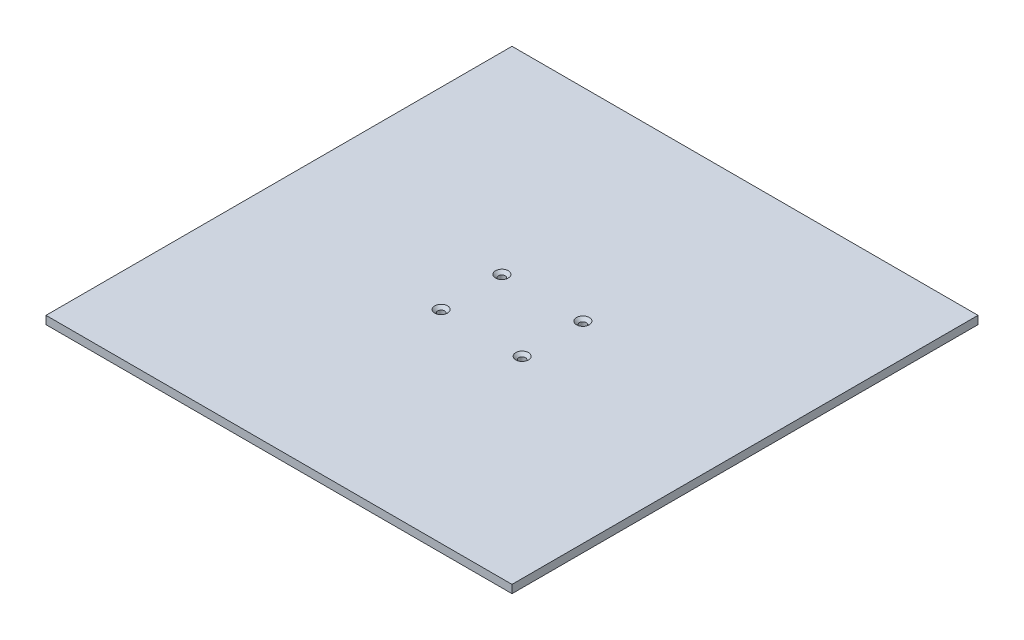
SolidWorks part; units mm, degrees
ref_plane "Front Plane" through (0, 0, 0) normal (0, 0, 1) x (1, 0, 0)
ref_plane "Top Plane" through (0, 0, 0) normal (0, 1, 0) x (1, 0, 0)
ref_plane "Right Plane" through (0, 0, 0) normal (1, 0, 0) x (0, 0, -1)
sketch "Sketch1" plane through (0, 0, 0) normal (0, 1, 0) x (1, 0, 0)
  line L1 (-115, -115) -> (115, -115)
  line L2 (-115, -115) -> (-115, 115)
  line L3 (-115, 115) -> (115, 115)
  line L4 (115, -115) -> (115, 115)
  line L5 (-115, -115) -> (115, 115) construction
  line L6 (-115, 115) -> (115, -115) construction
  point P0 (0, 0)
  dimension "D1" = 230
extrude "Boss-Extrude1" add sketch "Sketch1" along normal mid plane 4
sketch "Sketch2" plane through (0, 2, 0) normal (0, 1, 0) x (1, 0, 0)
  line L1 (-20, -15) -> (20, -15) construction
  line L2 (-20, -15) -> (-20, 15) construction
  line L3 (-20, 15) -> (20, 15) construction
  line L4 (20, -15) -> (20, 15) construction
  line L5 (-20, -15) -> (20, 15) construction
  line L6 (-20, 15) -> (20, -15) construction
  point P0 (0, 0)
  dimension "D1" = 40
  dimension "D2" = 30
hole_wizard "CSK for M3 Flat Head Machine Screw1" positions "Sketch3" profile "Sketch4" countersink size "M3" standard "ANSI Metric" end condition up to next
sketch "Sketch3" plane through (0, 2, 0) normal (0, 1, 0) x (1, 0, 0)
  point P0 (-20, 15)
  point P3 (20, 15)
  point P6 (20, -15)
  point P9 (-20, -15)
sketch "Sketch4" plane through (-20, 2, -15) normal (1, 0, 0) x (0, 0, 1)
  line L0 (0, 0) -> (0, 4)
  line L1 (0, 4) -> (1.7, 4)
  line L2 (1.7, 4) -> (1.7, 1.45)
  line L3 (1.7, 1.45) -> (3.15, 0)
  line L5 (3.15, 0) -> (0, 0)
  line L6 (-1.7, 1.45) -> (-3.15, 0) construction
  line L11 (0, -6.35) -> (0, 107.95) construction
  dimension "Thru Hole Dia." = 3.4
  dimension "Thru Hole Depth" = 4
  dimension "Near C'Sink Dia." = 6.3
  dimension "Near C'Sink Angle" = 90
